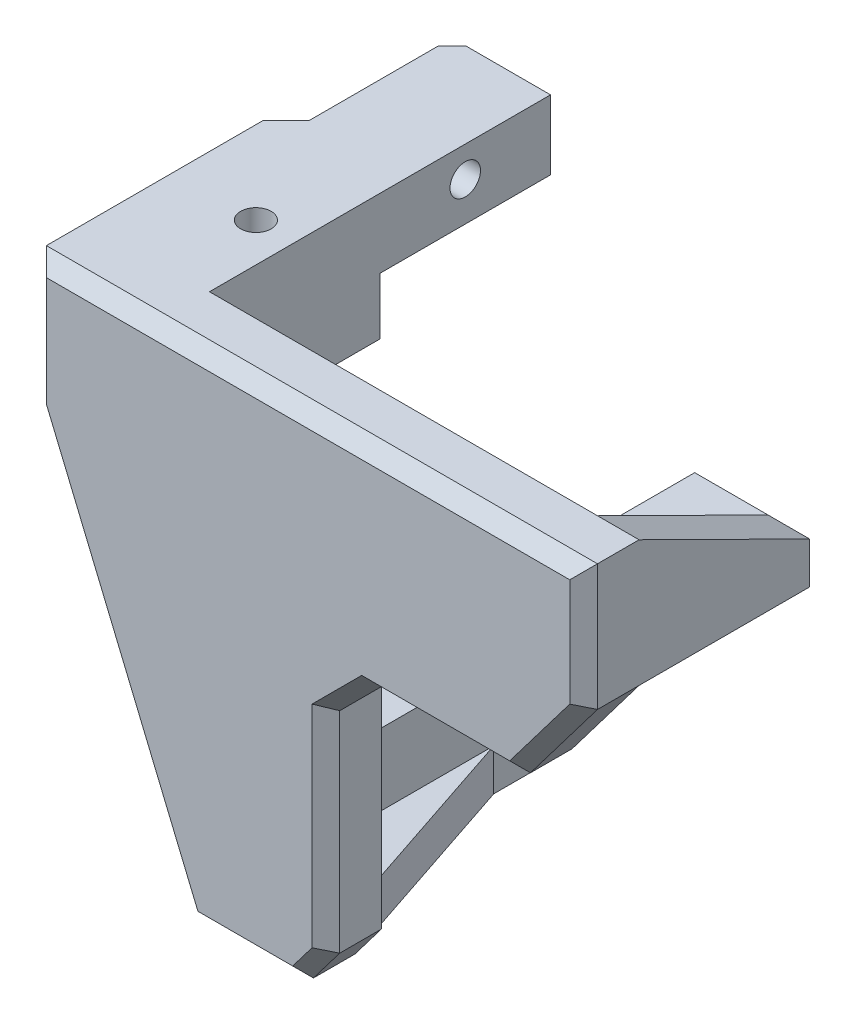
SolidWorks part; units mm, degrees
note: The reader was unsure of these and kept them because the rebuilt part matched: shared geometry of "Sketch1<5>".
ref_plane "Front Plane" through (0, 0, 0) normal (0, 0, 1) x (1, 0, 0)
ref_plane "Top Plane" through (0, 0, 0) normal (0, 1, 0) x (1, 0, 0)
ref_plane "Right Plane" through (0, 0, 0) normal (1, 0, 0) x (0, 0, -1)
sketch "Sketch1" plane through (0, 0, 0) normal (0, 0, 1) x (1, 0, 0)
  line L0 (22.225, 18.256) -> (26.6434, 18.256) construction
  line L1 (26.9875, 18.006) -> (26.9875, 16.2191) construction
  line L2 (22.225, 18.256) -> (26.6434, 18.256)
  line L3 (26.9875, 18.006) -> (26.9875, 16.2191)
  line L4 (7.4802, 22.225) -> (21.8809, 22.225) construction
  line L5 (7.4802, 22.225) -> (21.8809, 22.225)
  line L6 (-4.5125, 18.256) -> (0, 18.256) construction
  line L7 (-4.7625, 16.125) -> (-4.7625, 17.9119) construction
  line L8 (-4.5125, 18.256) -> (0, 18.256)
  line L9 (-4.7625, 16.125) -> (-4.7625, 17.9119)
  line L10 (26.9875, 17.1125) -> (30.9875, 17.1125) construction
  line L11 (-4.7625, 17.0185) -> (-8.7625, 17.0185) construction
  line L12 (0, 18.256) -> (-8.7625, 18.256)
  line L14 (2.25, 27.356) -> (0.25, 27.356) construction
  line L15 (-8.7625, 18.256) -> (-8.7625, 27.356)
  line L16 (-8.7625, 27.356) -> (30.9875, 27.356)
  line L17 (30.9875, 27.356) -> (30.9875, 18.256)
  line L18 (30.9875, 18.256) -> (0, 18.256)
  line L20 (2.131, -4.7625) -> (0.3441, -4.7625) construction
  line L21 (2.5, -0.594) -> (2.5, -5.094) construction
  line L22 (2.131, -4.7625) -> (0.3441, -4.7625)
  line L23 (1.2375, -4.7625) -> (1.2375, -8.7625) construction
  line L24 (2.5, -0.594) -> (5.5, -0.594)
  line L25 (5.5, -0.594) -> (5.5, -8.7625)
  line L26 (5.5, -8.7625) -> (2.5, -8.7625)
  line L27 (2.5, -8.7625) -> (2.5, -0.594)
  line L28 (5.5, -8.7625) -> (10.5, -8.7625)
  line L29 (10.5, -8.7625) -> (30.9875, 18.256)
  line L30 (2.5, -8.7625) -> (-8.7625, 18.256)
  line L31 (26.1538, 11.8814) -> (12.3961, 11.8814)
  line L32 (12.3961, 11.8814) -> (12.3961, -6.2619)
  line L33 (2.25, 27.356) -> (0.25, 27.356)
  line L34 (2.5, -0.594) -> (2.5, -5.094)
  line L35 (2.5, -0.594) -> (2.5, -5.094)
  dimension "D1" = 4
  dimension "D2" = 4
  dimension "D3" = 4
  dimension "D4" = 3
  dimension "D5" = 5
  dimension "D6" = 8
extrude "Boss-Extrude1" add sketch "Sketch1" along normal blind 4
extrude "Boss-Extrude2" add sketch "Sketch1<5>" against normal up to surface (24.6 mm away)
sketch "Sketch1<5>" plane through (0, 0, 0) normal (0, 0, 1) x (1, 0, 0) same geometry as "Sketch1"
sketch "Sketch2" plane through (0, 0, 0) normal (0, 0, -1) x (-1, 0, 0)
  line L0 (-22.7, 18.256) -> (-30.9875, 18.256)
  line L1 (-30.9875, 18.256) -> (-30.9875, 21.256)
  line L2 (-30.9875, 27.356) -> (-30.9875, 18.256) construction
  line L3 (-30.9875, 21.256) -> (-22.7, 21.256)
  line L4 (-22.7, 21.256) -> (-22.7, 18.256)
  line L5 (-22.7, 18.256) -> (-27.45, 18.256) construction
  line L6 (-22.7, 18.256) -> (-27.45, 18.256)
  line M5 (-30.9875, 27.356) -> (-30.9875, 18.256)
  dimension "D1" = 3
extrude "Boss-Extrude3" add sketch "Sketch2" along direction (0, 0, 1) on the side of the normal up to surface (12.3 mm away) contours L4 L3 L0 M5
sketch "Sketch3" plane through (0, 0, 0) normal (0, 0, -1) x (-1, 0, 0)
  line L1 (4.75, 18.256) -> (0, 18.256) construction
  line L3 (0, 22.106) -> (0, 18.006) construction
  line L4 (4.75, 18.256) -> (8.7625, 18.256)
  line L6 (4.75, 18.256) -> (0, 18.256)
  line L7 (0, 22.106) -> (0, 18.006)
  line L8 (8.7625, 18.256) -> (8.7625, 27.356)
  line L9 (8.7625, 27.356) -> (0, 27.356)
  line L10 (8.7625, 27.356) -> (-30.9875, 27.356) construction
  line L11 (0, 27.356) -> (0, 18.256)
  line M8 (8.7625, 18.256) -> (8.7625, 27.356)
  line M20 (8.7625, 27.356) -> (-30.9875, 27.356)
extrude "Boss-Extrude4" add sketch "Sketch3" along direction (0, 0, 1) on the side of the normal up to surface (12.3 mm away) contours L11 L7 L6 L4 M20 M8
sketch "Sketch4" plane through (0, 0, -12.3) normal (0, 0, -1) x (-1, 0, 0)
  line L1 (8.7625, 18.256) -> (0, 18.256) construction
  line L3 (4.1, -0.094) -> (4.1, 22.106) construction
  line L4 (4.1, -0.094) -> (4.1, 22.106)
  line L5 (3.85, 22.356) -> (-0.25, 22.356) construction
  line L6 (3.85, 22.356) -> (-0.25, 22.356)
  line L7 (4.1, 22.106) -> (4.1, 22.356)
  line L9 (4.1, 18.256) -> (7.1, 18.256)
  line L10 (7.1, 18.256) -> (7.1, 27.356)
  line L12 (7.1, 27.356) -> (0, 27.356)
  line L13 (4.1, 22.356) -> (3.85, 22.356)
  dimension "D1" = 3
extrude "Boss-Extrude5" add sketch "Sketch4" along direction (0, 0, -1) on the side of the normal up to surface (12.3 mm away)
sketch "Sketch5" plane through (0, -8.7625, 0) normal (0, -1, 0) x (1, 0, 0)
  line L0 (10.5, 0) -> (5.5, -15)
  line L1 (5.5, -24.6) -> (5.5, 0) construction
  line L2 (5.5, -15) -> (5, -15)
  line L3 (10.5, 0) -> (10.5, 0.5)
  line L4 (10.5, 4) -> (10.5, 0) construction
  line L5 (10.5, 0.5) -> (5, 0.5)
  line L6 (5, 0.5) -> (5, -15)
  line L7 (5, -15) -> (4.9134, -14.9954)
  line M4 (5.5, -24.6) -> (5.5, 0)
  line M5 (5.5, 0) -> (10.5, 0)
  dimension "D1" = 15
  dimension "D2" = 0.5
  dimension "D3" = 0.5
extrude "Boss-Extrude6" add sketch "Sketch5" against normal blind 3 contours L0 M5 M4
chamfer "Chamfer1" distance 4 angle 45 1 edges at (4, -8.7625, -24.6)
chamfer "Chamfer4" distance 2 angle 45 1 edges
chamfer "Chamfer5" distance 1 angle 45 5 edges at (-7.9312, 18.256, -13.4688) (-8.7625, 18.256, -6.3188) (-7.1, 22.806, -24.6)
sketch "Sketch6" plane through (30.9875, 0, 0) normal (1, 0, 0) x (0, 0, -1)
  line L0 (12.3, 21.256) -> (0, 27.356)
  line L1 (0, 27.356) -> (-0.5, 27.356)
  line L3 (12.3, 21.256) -> (12.3, 20.756)
  line L4 (12.3, 18.256) -> (12.3, 21.256) construction
  line L5 (12.3, 20.756) -> (-0.5, 20.756)
  line L6 (-0.5, 20.756) -> (-0.5, 27.356)
  line L7 (-4, 27.356) -> (0, 27.356) construction
  dimension "D1" = 0.5
  dimension "D2" = 0.5
extrude "Boss-Extrude7" add sketch "Sketch6" against normal blind 3
chamfer "Chamfer8" distance 3 angle 45 1 edges at (12.3961, 11.8814, 2)
chamfer "Chamfer7" distance 1 angle 45 12 edges at (30.9875, 22.806, 4) (28.5706, 15.0687, 4) (11.4481, -7.5122, 4) (6.5, -8.7625, 4) (-3.1312, 4.7468, 0) (-3.1312, 4.7468, 4) (-8.7625, 18.756, 0) (-8.7625, 22.806, 4) (20.775, 11.8814, 4) (12.3961, 1.3097, 4) (13.8961, 10.3814, 4) (11.1125, 27.356, 4)
sketch "Sketch7" plane through (2.5, 0, 0) normal (-1, 0, 0) x (0, 0, 1)
  arc A0 (-18.2, -4.2152) -> (-18.7, -4.2152) centre (-18.45, -3.144) ccw construction
  arc A1 (-18.2, -4.2152) -> (-18.7, -4.2152) centre (-18.45, -3.144) ccw
  circle A2 centre (-18.45, -3.144) radius 1.1
extrude "Cut-Extrude1" cut sketch "Sketch7" against normal up to next contours A1 A2
sketch "Sketch8" plane through (0, 0, 0) normal (1, 0, 0) x (0, 0, -1)
  arc A0 (18.2, 26.2272) -> (18.7, 26.2272) centre (18.45, 25.156) ccw construction
  arc A1 (18.2, 26.2272) -> (18.7, 26.2272) centre (18.45, 25.156) ccw
  circle A2 centre (18.45, 25.156) radius 1.1
extrude "Cut-Extrude2" cut sketch "Sketch8" against normal up to next contours A1 A2
sketch "Sketch9" plane through (0, 18.256, 0) normal (0, -1, 0) x (1, 0, 0)
  arc A0 (-3.8712, -6.4) -> (-3.8712, -5.9) centre (-2.8, -6.15) ccw construction
  arc A1 (-3.8712, -6.4) -> (-3.8712, -5.9) centre (-2.8, -6.15) ccw
  circle A2 centre (-2.8, -6.15) radius 1.1
extrude "Cut-Extrude3" cut sketch "Sketch9" against normal up to next contours A1 A2
sketch "Sketch10" plane through (0, 18.256, 0) normal (0, -1, 0) x (1, 0, 0)
  arc A0 (26.5712, -5.9) -> (26.5712, -6.4) centre (25.5, -6.15) ccw construction
  arc A1 (26.5712, -5.9) -> (26.5712, -6.4) centre (25.5, -6.15) ccw
  circle A2 centre (25.5, -6.15) radius 1.1
extrude "Cut-Extrude4" cut sketch "Sketch10" against normal up to next contours A1 A2
